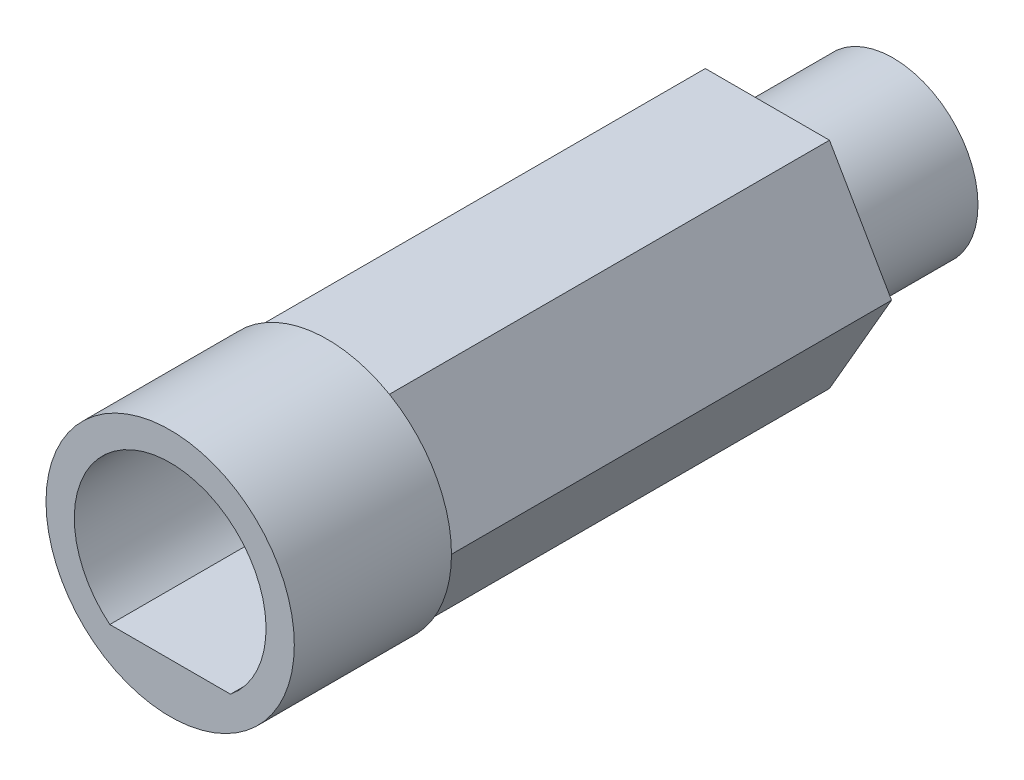
SolidWorks part; units mm, degrees
ref_plane "Front Plane" through (0, 0, 0) normal (0, 0, 1) x (1, 0, 0)
ref_plane "Top Plane" through (0, 0, 0) normal (0, 1, 0) x (1, 0, 0)
ref_plane "Right Plane" through (0, 0, 0) normal (1, 0, 0) x (0, 0, -1)
sketch "Sketch1" plane through (0, 0, 0) normal (0, 0, 1) x (1, 0, 0)
  line L1 (3.95, 0) -> (1.975, 3.4208)
  line L2 (1.975, 3.4208) -> (-1.975, 3.4208)
  line L3 (-1.975, 3.4208) -> (-3.95, 0)
  line L4 (-3.95, 0) -> (-1.975, -3.4208)
  line L5 (-1.975, -3.4208) -> (1.975, -3.4208)
  line L6 (1.975, -3.4208) -> (3.95, 0)
  circle A0 centre (0, 0) radius 3.95 construction
  circle A1 centre (0, 0) radius 3.4208 construction
  dimension "D1" = 7.9
extrude "Boss-Extrude1" add sketch "Sketch1" along normal blind 14
sketch "Sketch2" plane through (0, 0, 14) normal (0, 0, 1) x (1, 0, 0)
  circle A0 centre (0, 0) radius 3.95
  dimension "D1" = 7.9
extrude "Boss-Extrude2" add sketch "Sketch2" along normal blind 5
sketch "Sketch3" plane through (0, 0, 0) normal (0, 0, -1) x (-1, 0, 0)
  circle A0 centre (0, 0) radius 2.7
  dimension "D1" = 5.4
extrude "Boss-Extrude3" add sketch "Sketch3" along normal blind 4
sketch "Sketch4" plane through (0, 0, 19) normal (0, 0, 1) x (1, 0, 0)
  line L0 (-1.9198, -2.37) -> (1.9198, -2.37)
  circle A0 centre (0, 0) radius 3.05
  dimension "D1" = 6.1
  dimension "D2" = 5.42
extrude "Cut-Extrude1" cut sketch "Sketch4" against normal blind 16 contours L0 A0 region at (0, 0.1719, 19)
